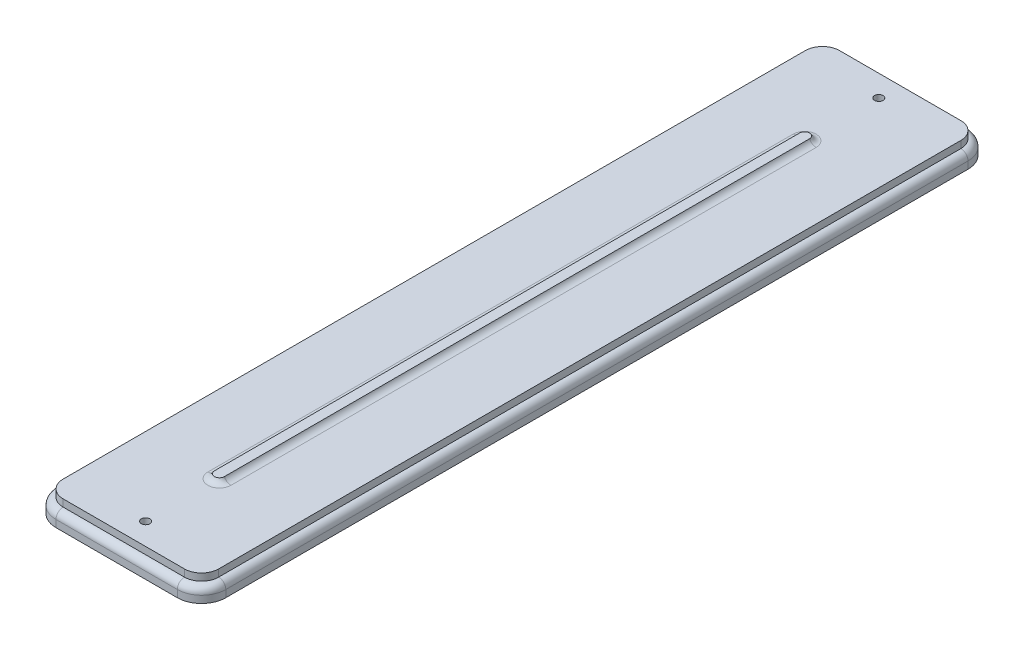
SolidWorks part; units mm, degrees
material "6061-T6 (SS)"
ref_plane "Ön Düzlem" through (0, 0, 0) normal (0, 0, 1) x (1, 0, 0)
ref_plane "Üst Düzlem" through (0, 0, 0) normal (0, 1, 0) x (1, 0, 0)
ref_plane "Sağ Düzlem" through (0, 0, 0) normal (1, 0, 0) x (0, 0, -1)
sketch "Sketch3" plane through (0, 0, 0) normal (0, 1, 0) x (1, 0, 0)
  line L0 (-42.5, 272) -> (42.5, 272)
  line L1 (-42.5, -272) -> (42.5, -272)
  line L2 (54.5, 260) -> (54.5, -260)
  line L3 (-54.5, 260) -> (-54.5, -260)
  arc A0 (-54.5, 260) -> (-42.5, 272) centre (-42.5, 260) cw
  arc A1 (42.5, 272) -> (54.5, 260) centre (42.5, 260) cw
  arc A2 (-54.5, -260) -> (-42.5, -272) centre (-42.5, -260) ccw
  arc A3 (42.5, -272) -> (54.5, -260) centre (42.5, -260) ccw
  circle A4 centre (0, 257) radius 3
  circle A5 centre (0, -256.72) radius 3
  point P12 (0, 272)
  point P15 (54.5, 0)
  point P20 (0, -272)
  dimension "D4" = 12
  dimension "D5" = 6
  dimension "D6" = 6
  dimension "D1" = 85
  dimension "D2" = 85
  dimension "D3" = 520
  dimension "D7" = 513.72
extrude "Boss-Extrude3" add sketch "Sketch3" against normal blind 5
sketch "Sketch4" plane through (0, 0, 0) normal (0, 1, 0) x (1, 0, 0)
  line L0 (-3.5, 205) -> (-3.5, -205)
  line L2 (3.5, -205) -> (3.5, 205)
  line L4 (42.5, 272) -> (-42.5, 272) construction
  line L5 (54.5, -260) -> (54.5, 260) construction
  arc A0 (-3.5, 205) -> (3.5, 205) centre (0, 205) cw
  arc A1 (-3.5, -205) -> (3.5, -205) centre (0, -205) ccw
  point P8 (0, 272)
  point P12 (54.5, 0)
  point P14 (3.5, 0)
  dimension "D1" = 3.5
  dimension "D2" = 410
extrude "Boss-Extrude4" add sketch "Sketch4" along normal blind 3
fillet "Fillet5" radius 5 4 edges at (0, 0, 208.5) (-3.5, 0, 0) (0, 0, -208.5) (3.5, 0, 0)
sketch "Sketch5" plane through (0, -5, 0) normal (0, -1, 0) x (1, 0, 0)
  line L0 (-42.5, 277) -> (42.5, 277)
  line L1 (59.5, 260) -> (59.5, -260)
  line L2 (-42.5, -277) -> (42.5, -277)
  line L3 (-59.5, 260) -> (-59.5, -260)
  line L4 (54.5, -260) -> (54.5, 260) construction
  line L5 (-54.5, 260) -> (-54.5, -260)
  line L6 (-42.5, -272) -> (42.5, -272)
  line L7 (54.5, -260) -> (54.5, 260)
  line L8 (-42.5, 272) -> (42.5, 272)
  arc A0 (-59.5, -260) -> (-42.5, -277) centre (-42.5, -260) ccw
  arc A1 (42.5, -277) -> (59.5, -260) centre (42.5, -260) ccw
  arc A2 (59.5, 260) -> (42.5, 277) centre (42.5, 260) ccw
  arc A3 (-59.5, 260) -> (-42.5, 277) centre (-42.5, 260) cw
  arc A4 (-54.5, 260) -> (-42.5, 272) centre (-42.5, 260) cw
  arc A5 (42.5, 272) -> (54.5, 260) centre (42.5, 260) cw
  arc A6 (-54.5, -260) -> (-42.5, -272) centre (-42.5, -260) ccw
  arc A7 (42.5, -272) -> (54.5, -260) centre (42.5, -260) ccw
  dimension "D1" = 5
extrude "Boss-Extrude5" add sketch "Sketch5" along normal blind 10 separate body
fillet "Fillet7" radius 5 8 edges at (-54.5208, -5, 272.0208) (0, -5, 277) (54.5208, -5, 272.0208) (59.5, -5, 0) (54.5208, -5, -272.0208) (0, -5, -277) (-54.5208, -5, -272.0208) (-59.5, -5, 0)
